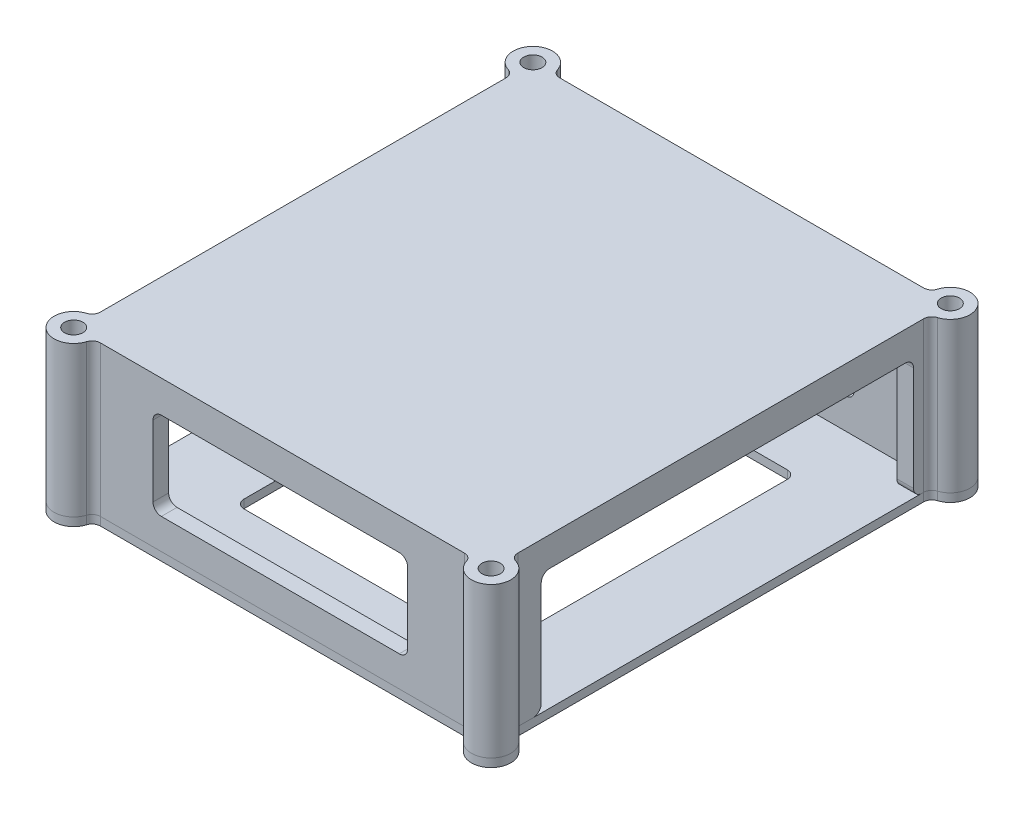
SolidWorks part; units mm, degrees
material "Nylon 101"
ref_plane "Front Plane" through (0, 0, 0) normal (0, 0, 1) x (1, 0, 0)
ref_plane "Top Plane" through (0, 0, 0) normal (0, 1, 0) x (1, 0, 0)
ref_plane "Right Plane" through (0, 0, 0) normal (1, 0, 0) x (0, 0, -1)
sketch "Sketch1" plane through (0, 0, 0) normal (0, 1, 0) x (1, 0, 0)
  line L1 (0, 0) -> (127, 0)
  line L2 (0, 0) -> (0, 139.7)
  line L3 (0, 139.7) -> (127, 139.7)
  line L4 (127, 0) -> (127, 139.7)
  dimension "D1" = 127
  dimension "D2" = 139.7
extrude "Boss-Extrude1" add sketch "Sketch1" along normal blind 45.72
sketch "Sketch3" plane through (0, 0, 0) normal (0, -1, 0) x (1, 0, 0)
  line L0 (0, -139.7) -> (0, 0) construction
  line L1 (6.35, -4.7625) -> (121.92, -4.7625)
  line L2 (6.35, -4.7625) -> (6.35, -135.8265)
  line L3 (6.35, -135.8265) -> (121.92, -135.8265)
  line L4 (121.92, -4.7625) -> (121.92, -135.8265)
  line L5 (0, 0) -> (127, 0) construction
  dimension "D1" = 115.57
  dimension "D2" = 131.064
  dimension "D3" = 6.35
  dimension "D4" = 4.7625
extrude "Cut-Extrude1" cut sketch "Sketch3" against normal blind 44
sketch "Sketch4" plane through (0, 0, -139.7) normal (0, 0, -1) x (-1, 0, 0)
  line L0 (-127, 0) -> (0, 0) construction
  line L1 (-101.6, 35.941) -> (-24.13, 35.941)
  line L2 (-101.6, 35.941) -> (-101.6, 9.271)
  line L3 (-101.6, 9.271) -> (-24.13, 9.271)
  line L4 (-24.13, 35.941) -> (-24.13, 9.271)
  line L7 (-127, 45.72) -> (-127, 0) construction
  dimension "D1" = 26.67
  dimension "D2" = 77.47
  dimension "D3" = 9.271
  dimension "D4" = 25.4
extrude "Cut-Extrude2" cut sketch "Sketch4" against normal blind 190.754
sketch "Sketch5" plane through (127, 0, 0) normal (1, 0, 0) x (0, 0, -1)
  line L0 (0, 45.72) -> (139.7, 45.72) construction
  line L1 (15.24, 36.83) -> (128.524, 36.83)
  line L2 (15.24, 36.83) -> (15.24, -10.16)
  line L3 (15.24, -10.16) -> (128.524, -10.16)
  line L4 (128.524, 36.83) -> (128.524, -10.16)
  line L6 (0, 45.72) -> (0, 0) construction
  dimension "D1" = 46.99
  dimension "D2" = 113.284
  dimension "D3" = 8.89
  dimension "D4" = 15.24
extrude "Cut-Extrude3" cut sketch "Sketch5" against normal blind 190.754 contours L2 L1 L4 L3
sketch "Sketch6" plane through (0, 0, 0) normal (0, -1, 0) x (-1, 0, 0)
  line L7 (-127, 139.7) -> (0, 139.7) construction
  line L8 (-127, 139.7) -> (-127, 0) construction
  line L9 (-127, 0) -> (0, 0) construction
  line L10 (0, 139.7) -> (0, 0) construction
  line L19 (-127, 0) -> (-127, 15.24) construction
  circle A0 centre (0, 0) radius 2.794
  circle A1 centre (-127, 0) radius 2.794
  circle A2 centre (0, 139.7) radius 2.794
  circle A3 centre (-127, 139.7) radius 2.794
  circle A8 centre (0, 139.7) radius 5.969
  circle A9 centre (-127, 139.7) radius 5.969
  circle A10 centre (-127, 0) radius 5.969
  circle A11 centre (0, 0) radius 5.969
  line M2 (-127, 15.24) -> (-127, 0)
  line M3 (-127, 0) -> (0, 0)
  line M4 (0, 0) -> (0, 15.24)
  dimension "D1" = 5.588
  dimension "D2" = 5.588
  dimension "D3" = 5.588
  dimension "D4" = 5.588
  dimension "D6" = 139.7
  dimension "D7" = 3.175
  dimension "D5" = 127
ref_plane "Plane1" through (63.5, 0, 0) normal (1, 0, 0) x (0, 0, -1)
ref_plane "Plane4" through (0, 0, -69.85) normal (0, 0, -1) x (-1, 0, 0)
extrude "Boss-Extrude2" add sketch "Sketch6" against normal through all contours A8 | A11 A0 M3 M4 | A8 A2 | A9 A3 | A10 A1 M2 M3 region at (-2.095, 0, -2.095) region at (131.1013, 0, 4.1013) region at (5.8002, 0, -139.7) region at (132.8002, 0, -139.7)
extrude "Cut-Extrude4" cut sketch "Sketch6<4>" against normal through all contours A0 M3 M4 | A1 M2 M3 | A1 M3 M2 | A0 M4 M3 | A2 | A3 region at (-0.3953, 0, 0.3953) region at (1.1858, 0, -1.1858) region at (125.8142, 0, -1.1858) region at (127.3953, 0, 0.3953) region at (0, 0, -139.7) region at (127, 0, -139.7)
sketch "Sketch6<4>" plane through (0, 0, 0) normal (0, -1, 0) x (-1, 0, 0) same geometry as "Sketch6"
fillet "Fillet1" radius 2.54 24 edges at (0, 22.86, -133.731) (127, 22.86, -5.969) (24.13, 9.271, -2.3813) (101.6, 9.271, -2.3813) (101.6, 35.941, -2.3813) (24.13, 35.941, -2.3813) (24.13, 9.271, -137.7632) (101.6, 9.271, -137.7632) (101.6, 35.941, -137.7632) (24.13, 35.941, -137.7632) (3.175, 0, -128.524) (3.175, 0, -15.24) (124.46, 0, -15.24) (124.46, 0, -128.524) (3.175, 36.83, -128.524) (124.46, 36.83, -15.24) (3.175, 36.83, -15.24) (124.46, 36.83, -128.524) (121.031, 22.86, 0) (5.969, 22.86, 0) (0, 22.86, -5.969) (121.031, 22.86, -139.7) (127, 22.86, -133.731) (5.969, 22.86, -139.7)
sketch "Sketch7" plane through (0, 0, 0) normal (0, -1, 0) x (1, 0, 0)
  line L49 (127, -131.5789) -> (127, -8.1211)
  line L50 (8.1211, -139.7) -> (118.8789, -139.7)
  line L51 (0, -8.1211) -> (0, -131.5789)
  line L52 (118.8789, 0) -> (8.1211, 0)
  line L53 (127, -131.5789) -> (127, -8.1211)
  line L54 (8.1211, -139.7) -> (118.8789, -139.7)
  line L55 (0, -8.1211) -> (0, -131.5789)
  line L56 (118.8789, 0) -> (8.1211, 0)
  line L59 (25.4, -23.8125) -> (25.4, -116.7765)
  line L60 (25.4, -116.7765) -> (102.87, -116.7765)
  line L61 (102.87, -116.7765) -> (102.87, -23.8125)
  line L62 (102.87, -23.8125) -> (25.4, -23.8125)
  line L63 (25.4, -23.8125) -> (25.4, -116.7765)
  line L64 (25.4, -116.7765) -> (102.87, -116.7765)
  line L65 (102.87, -116.7765) -> (102.87, -23.8125)
  line L66 (102.87, -23.8125) -> (25.4, -23.8125)
  circle A32 centre (127, 0) radius 2.794 construction
  circle A33 centre (127, 0) radius 2.794
  circle A34 centre (127, -139.7) radius 2.794 construction
  circle A35 centre (127, -139.7) radius 2.794
  circle A36 centre (0, 0) radius 2.794 construction
  circle A37 centre (0, -139.7) radius 2.794 construction
  circle A38 centre (0, 0) radius 2.794
  circle A39 centre (0, -139.7) radius 2.794
  arc A44 (128.7818, -5.6969) -> (121.3031, 1.7818) centre (127, 0) ccw
  arc A45 (128.7818, -5.6969) -> (127, -8.1211) centre (129.54, -8.1211) ccw
  arc A46 (127, -131.5789) -> (128.7818, -134.0031) centre (129.54, -131.5789) ccw
  arc A47 (121.3031, -141.4818) -> (128.7818, -134.0031) centre (127, -139.7) ccw
  arc A48 (121.3031, -141.4818) -> (118.8789, -139.7) centre (118.8789, -142.24) ccw
  arc A49 (8.1211, -139.7) -> (5.6969, -141.4818) centre (8.1211, -142.24) ccw
  arc A50 (-1.7818, -134.0031) -> (5.6969, -141.4818) centre (0, -139.7) ccw
  arc A51 (-1.7818, -134.0031) -> (0, -131.5789) centre (-2.54, -131.5789) ccw
  arc A52 (0, -8.1211) -> (-1.7818, -5.6969) centre (-2.54, -8.1211) ccw
  arc A53 (5.6969, 1.7818) -> (-1.7818, -5.6969) centre (0, 0) ccw
  arc A54 (5.6969, 1.7818) -> (8.1211, 0) centre (8.1211, 2.54) ccw
  arc A55 (118.8789, 0) -> (121.3031, 1.7818) centre (118.8789, 2.54) ccw
  arc A56 (128.7818, -5.6969) -> (121.3031, 1.7818) centre (127, 0) ccw
  arc A57 (128.7818, -5.6969) -> (127, -8.1211) centre (129.54, -8.1211) ccw
  arc A58 (127, -131.5789) -> (128.7818, -134.0031) centre (129.54, -131.5789) ccw
  arc A59 (121.3031, -141.4818) -> (128.7818, -134.0031) centre (127, -139.7) ccw
  arc A60 (121.3031, -141.4818) -> (118.8789, -139.7) centre (118.8789, -142.24) ccw
  arc A61 (8.1211, -139.7) -> (5.6969, -141.4818) centre (8.1211, -142.24) ccw
  arc A62 (-1.7818, -134.0031) -> (5.6969, -141.4818) centre (0, -139.7) ccw
  arc A63 (-1.7818, -134.0031) -> (0, -131.5789) centre (-2.54, -131.5789) ccw
  arc A64 (0, -8.1211) -> (-1.7818, -5.6969) centre (-2.54, -8.1211) ccw
  arc A65 (5.6969, 1.7818) -> (-1.7818, -5.6969) centre (0, 0) ccw
  arc A66 (5.6969, 1.7818) -> (8.1211, 0) centre (8.1211, 2.54) ccw
  arc A67 (118.8789, 0) -> (121.3031, 1.7818) centre (118.8789, 2.54) ccw
  dimension "D1" = 0
  dimension "D2" = 19.05
extrude "Boss-Extrude3" add sketch "Sketch7" along normal blind 2.54 separate body
fillet "Fillet2" radius 2.54 4 edges at (25.4, -1.27, -116.7765) (102.87, -1.27, -116.7765) (25.4, -1.27, -23.8125) (102.87, -1.27, -23.8125)
